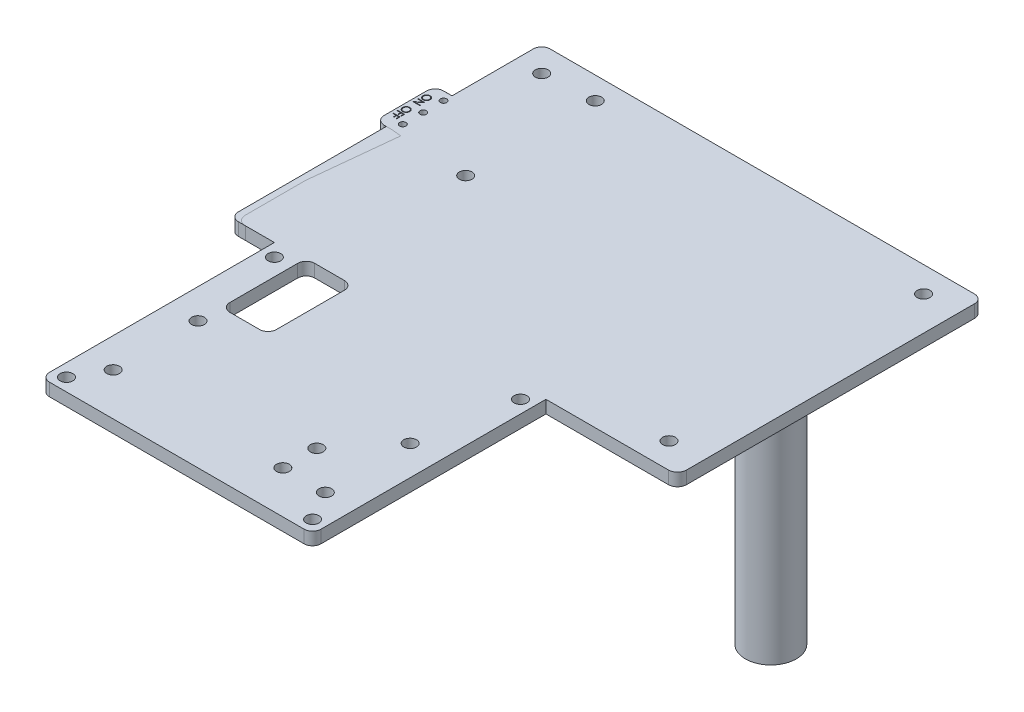
SolidWorks part; units mm, degrees
ref_plane "Front Plane" through (0, 0, 0) normal (0, 0, 1) x (1, 0, 0)
ref_plane "Top Plane" through (0, 0, 0) normal (0, 1, 0) x (1, 0, 0)
ref_plane "Right Plane" through (0, 0, 0) normal (1, 0, 0) x (0, 0, -1)
sketch "Sketch1" plane through (0, 0, 0) normal (0, 1, 0) x (1, 0, 0)
  line L0 (-32, 0) -> (47.619, 0) construction
  line L1 (30, 27.5) -> (-30, 27.5)
  line L2 (32, 25.5) -> (32, -25.5)
  line L3 (30, -27.5) -> (-30, -27.5)
  line L4 (-32, 25.5) -> (-32, -25.5)
  line L5 (32, 27.5) -> (-32, -27.5) construction
  line L6 (32, -27.5) -> (-32, 27.5) construction
  line L7 (29, 24.5) -> (-29, 24.5) construction
  line L8 (29, 24.5) -> (29, -24.5) construction
  line L9 (29, -24.5) -> (-29, -24.5) construction
  line L10 (-29, 24.5) -> (-29, -24.5) construction
  line L11 (29, 24.5) -> (-29, -24.5) construction
  line L12 (29, -24.5) -> (-29, 24.5) construction
  line L13 (0, 23.619) -> (0, -41.2698) construction
  line L14 (-32, 25.5) -> (-32, 27.5)
  line L15 (-32, 27.5) -> (-30, 27.5)
  line L16 (30, 27.5) -> (32, 27.5)
  line L17 (32, 27.5) -> (32, 25.5)
  circle A0 centre (-29, 24.5) radius 1.5
  circle A1 centre (29, 24.5) radius 1.5
  circle A2 centre (29, -24.5) radius 1.5
  circle A3 centre (-29, -24.5) radius 1.5
  arc A4 (-30, -27.5) -> (-32, -25.5) centre (-30, -25.5) cw
  arc A5 (32, -25.5) -> (30, -27.5) centre (30, -25.5) cw
  point P0 (0, 0)
  point P6 (0, 0)
  dimension "D5" = 3
  dimension "D6" = 2
  dimension "D1" = 64
  dimension "D2" = 55
  dimension "D3" = 58
  dimension "D4" = 49
extrude "Boss-Extrude1" add sketch "Sketch1" along normal blind 3
sketch "Sketch2" plane through (0, 3, 0) normal (0, 1, 0) x (1, 0, 0)
  line L0 (-29, 24.5) -> (-41, 24.5) construction
  line L1 (29, 24.5) -> (63, 24.5) construction
  line L2 (-41, 29.6496) -> (-41, 97.5)
  line L3 (63, 29.6496) -> (63, 97.5)
  line L4 (61, 99.5) -> (-39, 99.5)
  line L5 (30, 27.5) -> (60.8504, 27.5)
  line L6 (-30, 27.5) -> (-38.8504, 27.5)
  line L7 (-30, 27.5) -> (30, 27.5)
  line L8 (-41, 27.5) -> (63, 27.5)
  arc A0 (63, 97.5) -> (61, 99.5) centre (61, 97.5) ccw
  arc A1 (-41, 97.5) -> (-39, 99.5) centre (-39, 97.5) cw
  arc A2 (-38.8504, 27.5) -> (-41, 29.6496) centre (-38.8504, 29.6496) cw
  arc A3 (63, 29.6496) -> (60.8504, 27.5) centre (60.8504, 29.6496) cw
  point P0 (-29, 24.5)
  point P4 (29, 24.5)
  point P20 (-41, 99.5)
  line M9 (32, 27.5) -> (-32, 27.5)
  dimension "D4" = 2
  dimension "D1" = 2.1496
extrude "Boss-Extrude2" add sketch "Sketch2" against normal blind 3 contours L6 L5 L3 L4 L2 M9 region at (11, 3, -63.5013)
sketch "Sketch3" plane through (0, 3, 0) normal (0, 1, 0) x (1, 0, 0)
  line L0 (29, 24.5) -> (29, 57) construction
  line L1 (-29, 24.5) -> (-29, 57) construction
  line L2 (-29, 24.5) -> (-36.5, 24.5) construction
  line L3 (-36.5, 24.5) -> (-36.5, 57) construction
  line L4 (-36.5, 57) -> (-29, 57) construction
  line L5 (29, 24.5) -> (55.5, 24.5) construction
  line L6 (55.5, 24.5) -> (55.5, 57) construction
  line L7 (55.5, 57) -> (29, 57) construction
  circle A0 centre (-36.5, 57) radius 1.5
  circle A1 centre (55.5, 57) radius 1.5
  point P0 (-29, 24.5)
  point P1 (29, 24.5)
  dimension "D4" = 3
  dimension "D6" = 3
  dimension "D1" = 32.5
  dimension "D2" = 32.5
  dimension "D3" = 7.5
  dimension "D5" = 26.5
extrude "Cut-Extrude1" cut sketch "Sketch3" against normal blind 3
sketch "Sketch4" plane through (0, 0, 0) normal (0, -1, 0) x (1, 0, 0)
  circle A0 centre (-36.5, -57) radius 6
  circle A1 centre (55.5, -57) radius 6
  circle A2 centre (-36.5, -57) radius 1.5
  circle A3 centre (55.5, -57) radius 1.5
  dimension "D1" = 12
  dimension "D2" = 12
extrude "Boss-Extrude3" add sketch "Sketch4" along normal blind 50
sketch "Sketch5" plane through (0, 3, 0) normal (0, 1, 0) x (1, 0, 0)
  line L0 (29, 24.5) -> (29, 33.5) construction
  line L1 (29, 33.5) -> (55, 33.5) construction
  line L2 (55, 33.5) -> (55, 93.5) construction
  line L3 (55, 93.5) -> (-35, 93.5) construction
  line L4 (-23.11, 93.5) -> (-23.11, 63.7) construction
  line L5 (-23.11, 93.5) -> (-23.11, 94.24)
  line L7 (55, 93.5) -> (-23.11, 93.5) construction
  circle A0 centre (55, 33.5) radius 1.5
  circle A1 centre (55, 93.5) radius 1.5
  circle A10 centre (-23.11, 63.7) radius 1.5
  circle A12 centre (-35, 93.5) radius 1.5
  circle A13 centre (-23.11, 94.24) radius 1.5
  point P0 (29, 24.5)
  dimension "D3" = 3
  dimension "D5" = 3
  dimension "D7" = 3
  dimension "D8" = 3
  dimension "D12" = 3
  dimension "D10" = 0.74
  dimension "D1" = 9
  dimension "D2" = 60
  dimension "D4" = 90
  dimension "D6" = 30.54
  dimension "D9" = 26
  dimension "D18" = 78.11
sketch "Sketch8" plane through (0, 3, 0) normal (0, 1, 0) x (1, 0, 0)
  line L0 (-32, -7.5) -> (32, -7.5) construction
  line L1 (-32, 27.5) -> (-32, -25.5) construction
  line L2 (-25, 2.5) -> (-25, -17.5) construction
  line L3 (0, 15.5384) -> (0, -36.4977) construction
  line L5 (32, -25.5) -> (32, 27.5) construction
  line L6 (-30, -27.5) -> (30, -27.5) construction
  circle A0 centre (-25, 2.5) radius 1.5
  circle A1 centre (-25, -17.5) radius 1.5
  circle A2 centre (25, -17.5) radius 1.5
  circle A3 centre (25, 2.5) radius 1.5
  point P8 (-25, -7.5)
  dimension "D3" = 3
  dimension "D4" = 3
  dimension "D1" = 7
  dimension "D2" = 20
  dimension "D5" = 20
extrude "Cut-Extrude3" cut sketch "Sketch8" against normal through all
extrude "Cut-Extrude4" cut sketch "Sketch5" against normal through all contours A12 | A13 | A0 | A1 | A10 region at (55, 3, -33.5) region at (-35, 3, -93.5) region at (-24.5676, 3, -94.24)
sketch "Sketch9" plane through (0, -50, 0) normal (0, -1, 0) x (1, 0, 0)
  line L1 (-36.5, -51) -> (-36.5, -72.8662)
  circle A1 centre (-36.5, -57) radius 6 construction
  circle A2 centre (-36.5, -57) radius 6 construction
ref_plane "Plane1" through (0, 0, -63) normal (0, 0, -1) x (-1, 0, 0)
sketch "Sketch10" plane through (0, 0, -63) normal (0, 0, -1) x (-1, 0, 0)
  line L0 (-55.5, -50) -> (-55.5, -22.5876) construction
  line L1 (-61.5, -50) -> (-49.5, -50) construction
  line L2 (35.1316, -50) -> (35.1316, -29.5072) construction
  line L3 (-49.5, -50) -> (-49.5, 0) construction
  line L4 (-51, -40) -> (-60, -40)
  line L5 (-51, -40) -> (-51, -44)
  line L6 (-51, -44) -> (-60, -44)
  line L7 (-60, -40) -> (-60, -44)
  line L8 (-51, -40) -> (-60, -44) construction
  line L9 (-51, -44) -> (-60, -40) construction
  line L12 (-49.5, -31.3199) -> (-49.5, -24.5641)
  line L13 (30.5, -33.4481) -> (30.5, -22.5876)
  line L14 (30.5, 0) -> (30.5, -50) construction
  line L15 (-49.5, -27.942) -> (-10, -27.942)
  line L16 (-10, -7.1029) -> (-10, -45) construction
  line L17 (31, -44) -> (40, -40) construction
  line L18 (31, -40) -> (40, -44) construction
  line L19 (35.5, -50) -> (35.5, -22.5876) construction
  line L20 (40, -40) -> (40, -44)
  line L21 (31, -44) -> (40, -44)
  line L22 (31, -40) -> (31, -44)
  line L23 (31, -40) -> (40, -40)
  point P6 (-55.5, -42)
  point P29 (35.5, -42)
  dimension "D1" = 8
  dimension "D2" = 4
  dimension "D3" = 9
  dimension "D4" = 80
  dimension "D5" = 39.5
extrude "Cut-Extrude5" cut sketch "Sketch10" against normal blind 9 contours L4 L7 L6 L5 | L23 L22 L21 L20 region at (55.5, -42, -63) region at (-35.5, -42, -63)
sketch "Sketch11" plane through (0, 3, 0) normal (0, 1, 0) x (1, 0, 0)
  circle A1 centre (55.5, 57) radius 1.5
  circle A2 centre (-36.5, 57) radius 1.5
extrude "Boss-Extrude4" add sketch "Sketch11" against normal blind 40 contours A2 | A1
sketch "Sketch12" plane through (0, 3, 0) normal (0, 1, 0) x (1, 0, 0)
  line L0 (0, -27.5) -> (0, 99.5) construction
  line L1 (-30, -27.5) -> (30, -27.5) construction
  line L2 (61, 99.5) -> (-39, 99.5) construction
ref_axis "Axis1" through (0, 3, 27.5) along (0, 0, -1)
sketch "Sketch13" plane through (0, 3, 0) normal (0, 1, 0) x (1, 0, 0)
  line L0 (-41, 63.5748) -> (63, 63.5748) construction
  line L1 (-41, 29.6496) -> (-41, 97.5) construction
  line L2 (-41, 60.9686) -> (-41, 97.5) construction
  line L3 (-41, 71.5748) -> (63, 71.5748)
  line L4 (-41, 76.3748) -> (-41, 66.7748) construction
  line L5 (63, 29.6496) -> (63, 97.5) construction
  line L6 (-37, 78.3748) -> (-43, 78.3748)
  line L7 (-37, 78.3748) -> (-37, 64.3748)
  line L8 (-37, 64.3748) -> (-43, 64.3748)
  line L9 (-45, 76.3748) -> (-45, 66.3748)
  line L10 (-37, 78.3748) -> (-45, 64.3748) construction
  line L11 (-37, 64.3748) -> (-45, 78.3748) construction
  circle A0 centre (-41, 76.3748) radius 0.75
  circle A1 centre (-41, 71.5748) radius 0.75
  circle A2 centre (-41, 66.7748) radius 0.75
  arc A3 (-43, 64.3748) -> (-45, 66.3748) centre (-43, 66.3748) cw
  arc A4 (-43, 78.3748) -> (-45, 76.3748) centre (-43, 76.3748) ccw
  point P7 (-41, 63.5748)
  point P10 (-41, 71.5748)
  line M27 (-41, 97.5) -> (-41, 29.6496)
  dimension "D3" = 1.5
  dimension "D4" = 1.5
  dimension "D5" = 1.5
  dimension "D8" = 2
  dimension "D2" = 4
  dimension "D6" = 14
  dimension "D7" = 8
  dimension "D9" = 4.8
  dimension "D10" = 4.8
  dimension "D11" = 4
  dimension "D12" = 8
extrude "Boss-Extrude6" add sketch "Sketch13" against normal blind 3 contours L6 A4 L9 A3 L8 A2 A1 A0 M27 | A2 L8 L7 L3 A1 M27 | A1 L3 L7 L6 A0 M27 region at (-38.9139, 3, -74.9796) region at (-38.9189, 3, -67.9606) region at (-43.0347, 3, -71.3645)
sketch "Sketch17" plane through (0, 3, 0) normal (0, 1, 0) x (1, 0, 0)
  line L0 (-41, 75.6248) -> (-41, 77.1248) construction
  line L1 (-41, 70.8248) -> (-41, 72.3248) construction
  line L2 (-41, 66.0248) -> (-41, 67.5248) construction
  circle A0 centre (-41, 76.3748) radius 0.75
  circle A1 centre (-41, 71.5748) radius 0.75
  circle A2 centre (-41, 66.7748) radius 0.75
  point P0 (-41, 76.3748)
  point P1 (-41, 71.5748)
  point P4 (-41, 66.7748)
  dimension "D1" = 1.5
  dimension "D2" = 1.5
  dimension "D3" = 1.5
extrude "Cut-Extrude9" cut sketch "Sketch17" against normal blind 3
sketch "Sketch18" plane through (0, 3, 0) normal (0, 1, 0) x (1, 0, 0)
  line L0 (-44.4142, 77.789) -> (-44.4142, 64.9606) construction
  arc A0 (-43, 78.3748) -> (-45, 76.3748) centre (-43, 76.3748) ccw construction
  arc A1 (-45, 66.3748) -> (-43, 64.3748) centre (-43, 66.3748) ccw construction
  text T0 "   ON  OFF" font "Century Gothic" height 1.6
extrude "Cut-Extrude10" cut sketch "Sketch18" against normal blind 3
sketch "Sketch21" plane through (0, 3, 0) normal (0, 1, 0) x (1, 0, 0)
  line L0 (-29, 24.5) -> (-25, 24.5)
  line L1 (-25, 24.5) -> (-25, 26)
  line L2 (-25, 28) -> (-25, 10)
  line L3 (-23, 8) -> (-16, 8)
  line L4 (-14, 10) -> (-14, 26)
  line L5 (-16, 28) -> (-23, 28)
  arc A0 (-25, 10) -> (-23, 8) centre (-23, 10) ccw
  arc A1 (-16, 8) -> (-14, 10) centre (-16, 10) ccw
  arc A2 (-14, 26) -> (-16, 28) centre (-16, 26) ccw
  arc A3 (-23, 28) -> (-25, 26) centre (-23, 26) ccw
  point P9 (-25, 8)
  point P12 (-14, 8)
  dimension "D5" = 2
  dimension "D6" = 2
  dimension "D1" = 4
  dimension "D2" = 20
  dimension "D3" = 3.5
  dimension "D4" = 11
extrude "Cut-Extrude11" cut sketch "Sketch21" against normal blind 3 contours L5 A3 L1 L2 A0 L3 A1 L4 A2 region at (-19.5, 3, -18)
sketch "Sketch22" plane through (0, 3, 0) normal (0, 1, 0) x (1, 0, 0)
  line L0 (25, -17.5) -> (15, -17.5) construction
  line L1 (15, -17.5) -> (15, -9.5) construction
  circle A0 centre (15, -9.5) radius 1.5
  circle A1 centre (15, -17.5) radius 1.5
  point P0 (25, -17.5)
  point P5 (15, -17.5)
  dimension "D3" = 3
  dimension "D4" = 3
  dimension "D1" = 10
  dimension "D2" = 8
extrude "Cut-Extrude12" cut sketch "Sketch22" against normal blind 3
sketch "Sketch23" plane through (0, 3, 0) normal (0, 1, 0) x (1, 0, 0)
  line L0 (-42.5, 57) -> (-42.5, 29.5)
  line L1 (-40.5, 27.5) -> (-38.8504, 27.5)
  line L2 (-42.5, 57) -> (-42.5, 64.3748)
  line L3 (-41, 64.3748) -> (-43, 64.3748) construction
  line L4 (-38.8504, 27.5) -> (-38.8504, 64.3748)
  line L5 (-38.8504, 64.3748) -> (-42.5, 64.3748)
  arc A0 (-41, 60.9686) -> (-41, 53.0314) centre (-36.5, 57) ccw construction
  arc A1 (-42.5, 29.5) -> (-40.5, 27.5) centre (-40.5, 29.5) ccw
  dimension "D1" = 2
extrude "Boss-Extrude8" add sketch "Sketch23" against normal blind 3 separate body
